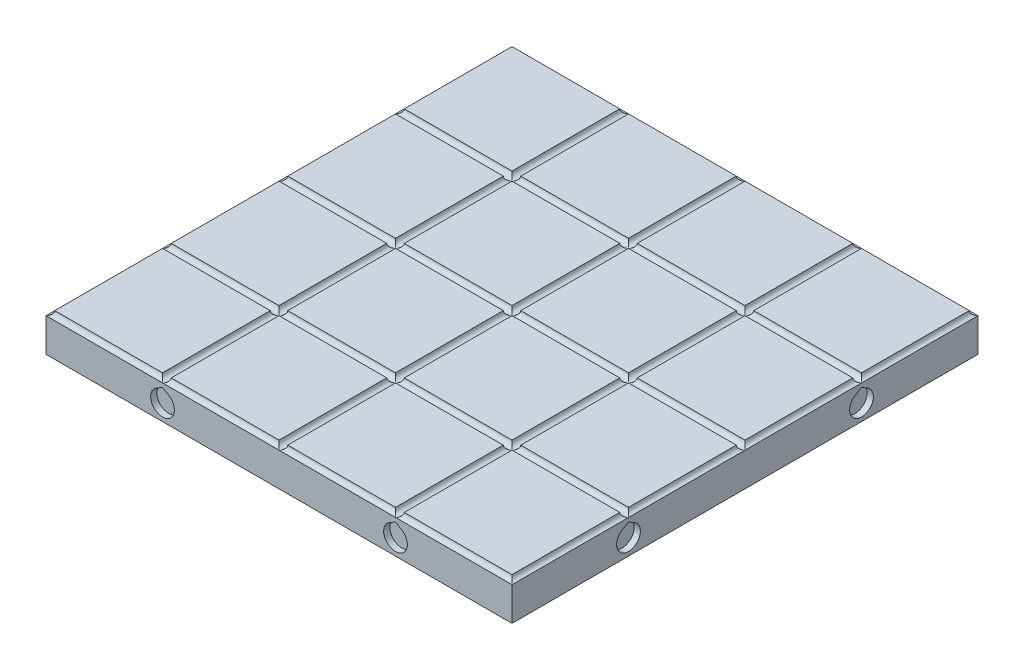
SolidWorks part; units mm, degrees
ref_plane "Спереди" through (0, 0, 0) normal (0, 0, 1) x (1, 0, 0)
ref_plane "Сверху" through (0, 0, 0) normal (0, 1, 0) x (1, 0, 0)
ref_plane "Справа" through (0, 0, 0) normal (1, 0, 0) x (0, 0, -1)
sketch "Эскиз1" plane through (0, 0, 0) normal (0, 1, 0) x (1, 0, 0)
  line L1 (80, -80) -> (-80, -80)
  line L2 (80, -80) -> (80, 80)
  line L3 (80, 80) -> (-80, 80)
  line L4 (-80, -80) -> (-80, 80)
  line L5 (0, 80) -> (0, -80) construction
  line L6 (80, 0) -> (-80, 0) construction
  point P0 (0, 0)
  dimension "D1" = 160
extrude "Бобышка-Вытянуть1" add sketch "Эскиз1" against normal blind 13
sketch "Эскиз2" plane through (0, 0, 0) normal (0, 1, 0) x (1, 0, 0)
  line L0 (-80, 80) -> (-80, -80)
sweep "Вырез-По траектории1" cut path "Эскиз2" circular profile diameter 3 parameters "D3"=3
pattern_linear "Линейный массив1" count 5 spacing 40 along (1, 0, 0) of "Вырез-По траектории1"
sketch "Эскиз180" plane through (0, 0, 0) normal (0, 1, 0) x (1, 0, 0)
  line L0 (-80, -80) -> (80, -80)
sweep "Вырез-По траектории2" cut path "Эскиз180" circular profile diameter 3 parameters "D3"=3
pattern_linear "Линейный массив2" count 5 spacing 40 along (1, 0, 0) count 5 spacing 40 along (0, 0, -1) of "Вырез-По траектории2"
sketch "Эскиз181" plane through (0, 0, 80) normal (0, 0, 1) x (1, 0, 0)
  line L0 (0, 22.1626) -> (0, -39.4564) construction
  line L3 (-40, -1.5) -> (-40, -13) construction
  line L4 (-80, -13) -> (80, -13) construction
  line L5 (40, -2.8598) -> (37.9625, -4.0361)
  line L8 (40, -2.8598) -> (42.0375, -4.0361)
  line L9 (-80, -13) -> (-80, -1.5) construction
  line L10 (-48.6563, -7.25) -> (-30.5924, -7.25) construction
  line L13 (-40, -2.8598) -> (-42.0375, -4.0361)
  line L14 (-80, -1.5) -> (-40, -1.5) construction
  line L15 (-40, -2.8598) -> (-37.9625, -4.0361)
  circle A2 centre (-40, -7.5652) radius 4.075
  circle A3 centre (40, -7.5652) radius 4.075
  point P22 (-40, -11.6402)
  dimension "D1" = 8.15
  dimension "D6" = 40
  dimension "D2" = 60
  dimension "D3" = 1.3598
  dimension "D4" = 1.3598
  dimension "D5" = 120
extrude "Вырез-Вытянуть1" cut sketch "Эскиз181" against normal blind 2.15 contours A2 | A2 L15 L13 | A3 | L5 A3 L8
pattern_circular "Круговой массив1" count 4 over 360 about axis through (0, -13, 0) along (0, -1, 0) of "Вырез-Вытянуть1" other way count 4
